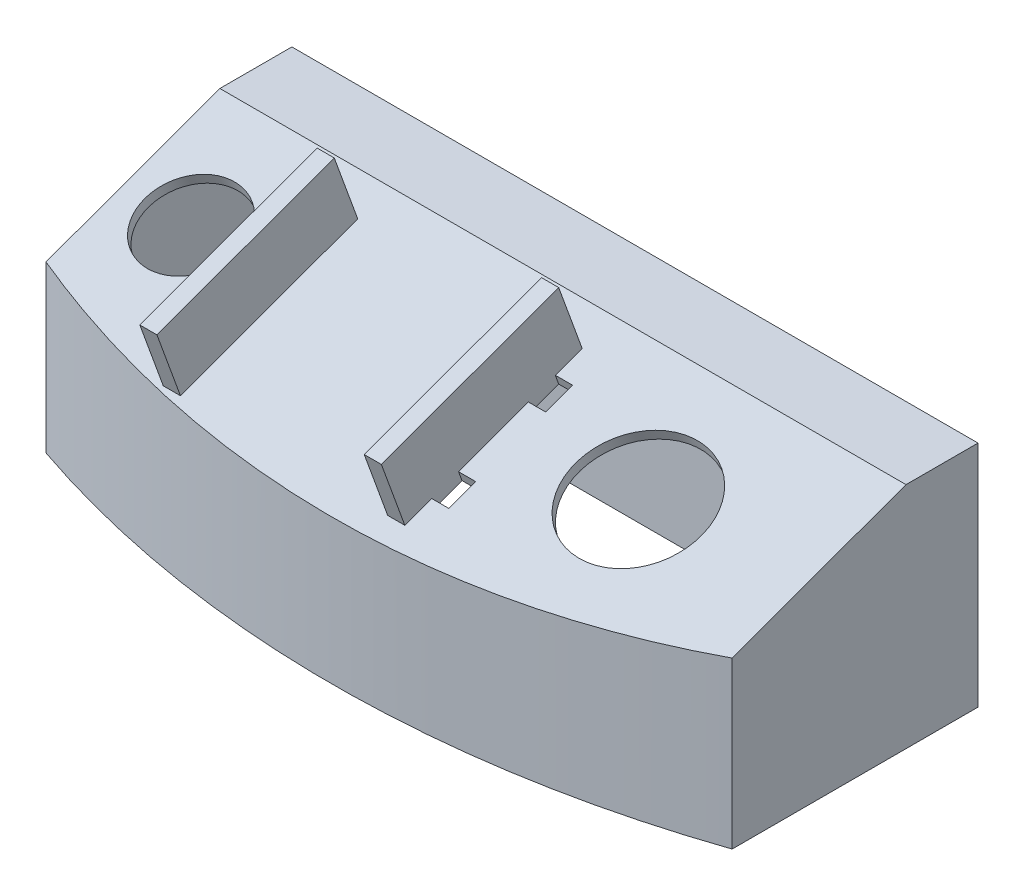
SolidWorks part; units mm, degrees
ref_plane "Front Plane" through (0, 0, 0) normal (0, 0, 1) x (1, 0, 0)
ref_plane "Top Plane" through (0, 0, 0) normal (0, 1, 0) x (1, 0, 0)
ref_plane "Right Plane" through (0, 0, 0) normal (1, 0, 0) x (0, 0, -1)
sketch "Sketch1" plane through (0, 0, 0) normal (0, 1, 0) x (1, 0, 0)
  line L0 (0, 0) -> (120, 0)
  line L1 (120, 0) -> (120, -43)
  line L2 (0, 0) -> (0, -43)
  line L3 (60, 0) -> (60, -53) construction
  arc A0 (0, -43) -> (120, -43) centre (60, 132) ccw
  point P7 (60, 0)
  dimension "D4" = 53
  dimension "D1" = 120
  dimension "D2" = 43
extrude "Boss-Extrude1" add sketch "Sketch1" along normal blind 40
sketch "Sketch2" plane through (120, 0, 0) normal (1, 0, 0) x (0, 0, -1)
  line L0 (-12.5932, 40) -> (-53, 25.2931)
  line L1 (-43, 40) -> (0, 40) construction
  line L2 (-53, 40) -> (-53, 0) construction
  line L3 (-53, 25.2931) -> (-53, 40)
  line L4 (-43, 40) -> (-53, 40) construction
  line L5 (-53, 40) -> (-12.5932, 40)
  dimension "D1" = 20
  dimension "D2" = 43
extrude "Cut-Extrude1" cut sketch "Sketch2" against normal through all
sketch "Sketch3" plane through (0, 39.3683, 14.3289) normal (0, 0.9397, 0.342) x (1, 0, 0)
  line L0 (92, 1.8471) -> (92, -38.1854) construction
  line L1 (69, -32.1529) -> (72, -32.1529)
  line L2 (0, 1.8471) -> (120, 1.8471) construction
  line L3 (72, -32.1529) -> (72, -27.1529)
  line L4 (60, 1.8471) -> (60, -41.1529) construction
  line L9 (66, -4.1529) -> (69, -4.1529)
  line L10 (66, -4.1529) -> (66, -37.1529)
  line L11 (66, -37.1529) -> (69, -37.1529)
  line L12 (69, -4.1529) -> (69, -9.1529)
  line L13 (72, -27.1529) -> (69, -27.1529)
  line L14 (69, -14.1529) -> (72, -14.1529)
  line L15 (72, -14.1529) -> (72, -9.1529)
  line L16 (72, -9.1529) -> (69, -9.1529)
  line L17 (47.875, 1.8471) -> (47.875, -40.7297) construction
  line L18 (69, -14.1529) -> (69, -27.1529)
  line L19 (69, -32.1529) -> (69, -37.1529)
  line L20 (26.75, -32.1529) -> (26.75, -37.1529)
  line L21 (26.75, -14.1529) -> (26.75, -27.1529)
  line L22 (23.75, -9.1529) -> (26.75, -9.1529)
  line L23 (23.75, -14.1529) -> (23.75, -9.1529)
  line L24 (26.75, -14.1529) -> (23.75, -14.1529)
  line L25 (23.75, -27.1529) -> (26.75, -27.1529)
  line L26 (26.75, -4.1529) -> (26.75, -9.1529)
  line L27 (29.75, -37.1529) -> (26.75, -37.1529)
  line L28 (29.75, -4.1529) -> (29.75, -37.1529)
  line L29 (29.75, -4.1529) -> (26.75, -4.1529)
  line L30 (23.75, -32.1529) -> (23.75, -27.1529)
  line L31 (26.75, -32.1529) -> (23.75, -32.1529)
  line L32 (12, 1.8471) -> (12, -34.4108) construction
  line L33 (0, -30.5112) -> (0, 1.8471) construction
  circle A0 centre (92, -18.1692) radius 11
  circle A2 centre (12, -16.2819) radius 8.1
  ellipse E1 centre (60, 155.7199) end of major axis (60, -41.1529) minor radius 185 (0, -30.5112) -> (120, -30.5112) ccw construction
  point P43 (0, 0)
  dimension "D1" = 22
  dimension "D13" = 16.2
  dimension "D2" = 23
  dimension "D3" = 6
  dimension "D4" = 6
  dimension "D5" = 3
  dimension "D6" = 33
  dimension "D7" = 5
  dimension "D8" = 3
  dimension "D9" = 18.125
  dimension "D10" = 5
  dimension "D11" = 5
  dimension "D14" = 12
extrude "Cut-Extrude3" cut sketch "Sketch3" against normal blind 1.75
sketch "Sketch5" plane through (0, 37.7238, 13.7303) normal (0, 0.9397, 0.342) x (1, 0, 0)
  circle A0 centre (92, -18.1692) radius 15
  dimension "D1" = 30
extrude "Cut-Extrude4" cut sketch "Sketch5" against normal through all
ref_plane "Plane1" through (118.25, 0, 0) normal (1, 0, 0) x (0, 0, -1)
sketch "Sketch9" plane through (118.25, 0, 0) normal (1, 0, 0) x (0, 0, -1)
  line L0 (-1.75, 0) -> (-1.75, 38.25)
  line L1 (-1.75, 38.25) -> (-12.2846, 38.25)
  line L2 (-12.2846, 38.25) -> (-41.9005, 27.4707)
  line L3 (-41.9005, 27.4707) -> (-41.9005, 0)
  line L4 (-41.9005, 0) -> (-1.75, 0)
  line L6 (0, 40) -> (0, 0) construction
  line L7 (-43, 28.9328) -> (-43, 0) construction
  line L8 (-43, 28.9328) -> (-12.5932, 40) construction
  line L9 (-12.5932, 40) -> (0, 40) construction
  line L10 (-43, 0) -> (0, 0) construction
  dimension "D1" = 1.75
  dimension "D2" = 1.0995
  dimension "D3" = 1.75
  dimension "D4" = 1.75
extrude "Cut-Extrude7" cut sketch "Sketch9" against normal offset from surface (116.5 mm away) 1.75 up to face at (0, 21.7866, 19.7186)
sketch "Sketch11" plane through (0, 39.3683, 14.3289) normal (0, 0.9397, 0.342) x (1, 0, 0)
  line L1 (26.75, -37.1529) -> (29.75, -37.1529)
  line L2 (26.75, -37.1529) -> (26.75, -4.1529)
  line L3 (26.75, -4.1529) -> (29.75, -4.1529)
  line L4 (29.75, -37.1529) -> (29.75, -4.1529)
  line L5 (66, -4.1529) -> (69, -4.1529)
  line L6 (66, -4.1529) -> (66, -37.1529)
  line L7 (66, -37.1529) -> (69, -37.1529)
  line L8 (69, -4.1529) -> (69, -37.1529)
extrude "Boss-Extrude2" add sketch "Sketch11" against normal up to surface (1.75 mm away) and the other way blind 12 up to face at (53.1346, 31.6939, 30.2973)
sketch "Sketch13" plane through (0, 0, 0) normal (0, -1, 0) x (1, 0, 0)
  line L0 (118.25, -22) -> (118.25, 22) construction
  line L1 (101.2494, 41.9005) -> (118.25, 41.9005) construction
  line L2 (1.75, 41.9005) -> (118.25, 41.9005)
  arc A0 (1.75, 41.9005) -> (118.25, 41.9005) centre (60, -132) cw
  arc A1 (120, 43) -> (0, 43) centre (60, -132) ccw construction
  dimension "D1" = 0
extrude "Cut-Extrude8" cut sketch "Sketch13" against normal up to surface (27.4707 mm away) up to face at (57.6429, 29.2087, 37.1253)
sketch "Sketch14" plane through (0, 0, 0) normal (0, -1, 0) x (1, 0, 0)
  line L0 (1.75, 1.75) -> (21.75, 1.75)
  line L1 (1.75, 1.75) -> (118.25, 1.75) construction
  line L2 (21.75, 1.75) -> (21.75, 47.3638)
  line L3 (1.75, 1.75) -> (1.75, 41.9005)
  line L4 (60, 0) -> (60, 53) construction
  line L5 (120, 0) -> (0, 0) construction
  line L6 (118.25, 1.75) -> (118.25, 41.9005)
  line L7 (98.25, 1.75) -> (98.25, 47.3638)
  line L8 (118.25, 1.75) -> (98.25, 1.75)
  arc A0 (118.25, 41.9005) -> (1.75, 41.9005) centre (60, -132) ccw construction
  arc A1 (118.25, 41.9005) -> (1.75, 41.9005) centre (60, -132) ccw construction
  arc A2 (1.75, 41.9005) -> (21.75, 47.3638) centre (60, -132) cw
  arc A3 (120, 43) -> (0, 43) centre (60, -132) ccw construction
  arc A4 (118.25, 41.9005) -> (98.25, 47.3638) centre (60, -132) ccw
  dimension "D1" = 20
extrude "Boss-Extrude3" add sketch "Sketch14" against normal blind 3
